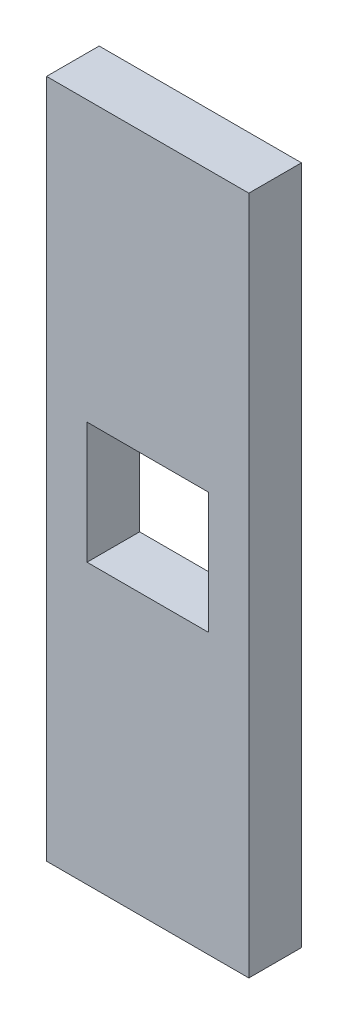
SolidWorks part; units mm, degrees
ref_plane "Front Plane" through (0, 0, 0) normal (0, 0, 1) x (1, 0, 0)
ref_plane "Top Plane" through (0, 0, 0) normal (0, 1, 0) x (1, 0, 0)
ref_plane "Right Plane" through (0, 0, 0) normal (1, 0, 0) x (0, 0, -1)
sketch "Sketch1" plane through (0, 0, 0) normal (0, 0, 1) x (1, 0, 0)
  line L0 (0, 67.2) -> (0, 44.8)
  line L1 (0, 67.2) -> (20, 67.2)
  line L2 (0, 44.8) -> (0, 39.6)
  line L3 (20, 0) -> (0, 0)
  line L4 (4, 39.6) -> (16, 39.6)
  line L5 (4, 27.6) -> (16, 27.6)
  line L6 (4, 39.6) -> (4, 27.6)
  line L7 (16, 39.6) -> (16, 27.6)
  line L8 (0, 44.8) -> (20, 44.8) construction
  line L9 (0, 39.6) -> (20, 39.6) construction
  line L10 (0, 39.6) -> (0, 27.6)
  line L11 (0, 27.6) -> (0, 22.4)
  line L12 (20, 44.8) -> (20, 39.6)
  line L13 (20, 67.2) -> (20, 44.8)
  line L14 (0, 22.4) -> (0, 0)
  line L15 (20, 39.6) -> (20, 27.6)
  line L16 (20, 27.6) -> (20, 22.4)
  line L17 (20, 22.4) -> (20, 0)
  line L18 (0, 27.6) -> (20, 27.6) construction
  line L19 (20, 22.4) -> (0, 22.4) construction
  line L20 (10, -0.0005) -> (10, 4.0956) construction
  point P18 (10, 27.6)
  point P20 (10, 39.6)
  point P21 (10, 67.2)
  dimension "D1" = 22.4
  dimension "D2" = 12
  dimension "D3" = 5.2
  dimension "D4" = 20
  dimension "D5" = 12
  dimension "D6" = 12
extrude "Boss-Extrude1" add sketch "Sketch1" along normal blind 5.2
